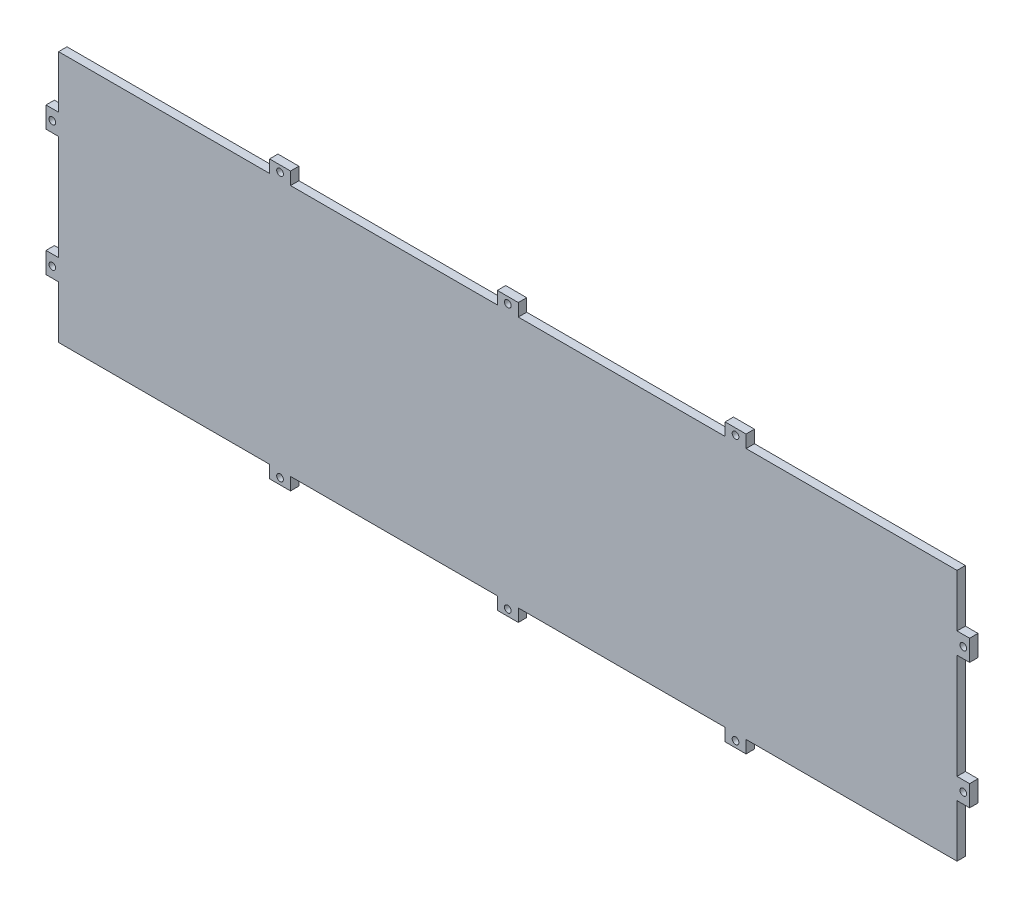
SolidWorks part; units mm, degrees
ref_plane "Front Plane" through (0, 0, 0) normal (0, 0, 1) x (1, 0, 0)
ref_plane "Top Plane" through (0, 0, 0) normal (0, 1, 0) x (1, 0, 0)
ref_plane "Right Plane" through (0, 0, 0) normal (1, 0, 0) x (0, 0, -1)
sketch "Sketch1" plane through (0, 0, 0) normal (0, 0, 1) x (1, 0, 0)
  line L0 (109.9, 127) -> (113.1, 127) construction
  line L1 (6, 250) -> (106.5, 250)
  line L2 (6, 250) -> (6, 225)
  line L3 (6, 130) -> (106.5, 130)
  line L4 (434, 250) -> (434, 225)
  line L5 (109.9, 130) -> (109.9, 124) construction
  line L6 (113.1, 124) -> (113.1, 130) construction
  line L7 (218.4, 127) -> (221.6, 127) construction
  line L8 (218.4, 130) -> (218.4, 124) construction
  line L9 (221.6, 124) -> (221.6, 130) construction
  line L10 (326.9, 127) -> (330.1, 127) construction
  line L11 (326.9, 130) -> (326.9, 124) construction
  line L12 (330.1, 124) -> (330.1, 130) construction
  line L13 (116.5, 130) -> (215, 130)
  line L14 (106.5, 124) -> (116.5, 124)
  line L15 (106.5, 124) -> (106.5, 130)
  line L16 (225, 130) -> (323.5, 130)
  line L17 (116.5, 124) -> (116.5, 130)
  line L18 (106.5, 124) -> (116.5, 130) construction
  line L19 (106.5, 130) -> (116.5, 124) construction
  line L20 (215, 124) -> (225, 124)
  line L21 (215, 124) -> (215, 130)
  line L22 (333.5, 130) -> (434, 130)
  line L23 (225, 124) -> (225, 130)
  line L24 (215, 124) -> (225, 130) construction
  line L25 (215, 130) -> (225, 124) construction
  line L26 (323.5, 124) -> (333.5, 124)
  line L27 (323.5, 124) -> (323.5, 130)
  line L28 (6, 190) -> (434, 190) construction
  line L29 (333.5, 124) -> (333.5, 130)
  line L30 (323.5, 124) -> (333.5, 130) construction
  line L31 (323.5, 130) -> (333.5, 124) construction
  line L32 (323.5, 256) -> (323.5, 250)
  line L33 (323.5, 256) -> (333.5, 256)
  line L34 (333.5, 256) -> (333.5, 250)
  line L35 (215, 256) -> (215, 250)
  line L36 (215, 256) -> (225, 256)
  line L37 (225, 256) -> (225, 250)
  line L38 (106.5, 256) -> (106.5, 250)
  line L39 (116.5, 256) -> (116.5, 250)
  line L40 (106.5, 256) -> (116.5, 256)
  line L41 (333.5, 250) -> (434, 250)
  line L42 (225, 250) -> (323.5, 250)
  line L43 (116.5, 250) -> (215, 250)
  line L44 (0, 250) -> (6, 190) construction
  line L45 (6, 215) -> (6, 165)
  line L46 (0, 215) -> (6, 215)
  line L47 (0, 215) -> (0, 225)
  line L48 (0, 225) -> (6, 225)
  line L49 (0, 250) -> (0, 225) construction
  line L50 (0, 215) -> (6, 225) construction
  line L51 (0, 225) -> (6, 215) construction
  line L52 (0, 155) -> (6, 155)
  line L53 (0, 165) -> (0, 155)
  line L54 (0, 165) -> (6, 165)
  line L55 (220, 190) -> (220, 221.6948) construction
  line L56 (440, 165) -> (434, 165)
  line L57 (440, 165) -> (440, 155)
  line L58 (440, 155) -> (434, 155)
  line L59 (440, 215) -> (434, 215)
  line L60 (440, 215) -> (440, 225)
  line L61 (440, 225) -> (434, 225)
  line L62 (6, 155) -> (6, 130)
  line L63 (434, 155) -> (434, 130)
  line L64 (434, 215) -> (434, 165)
  circle A0 centre (111.5, 127) radius 1.6
  circle A1 centre (220, 127) radius 1.6
  circle A2 centre (328.5, 127) radius 1.6
  circle A3 centre (328.5, 253) radius 1.6
  circle A4 centre (220, 253) radius 1.6
  circle A5 centre (111.5, 253) radius 1.6
  circle A6 centre (3, 220) radius 1.6
  circle A7 centre (3, 160) radius 1.6
  circle A8 centre (437, 220) radius 1.6
  circle A9 centre (437, 160) radius 1.6
  point P24 (111.5, 127)
  point P29 (220, 127)
  point P34 (328.5, 127)
  point P47 (106.5, 127)
  point P66 (106.5, 253)
  point P68 (3, 220)
  dimension "D3" = 3.2
  dimension "D1" = 10
  dimension "D2" = 10
extrude "Boss-Extrude1" add sketch "Sketch1" against normal blind 4
